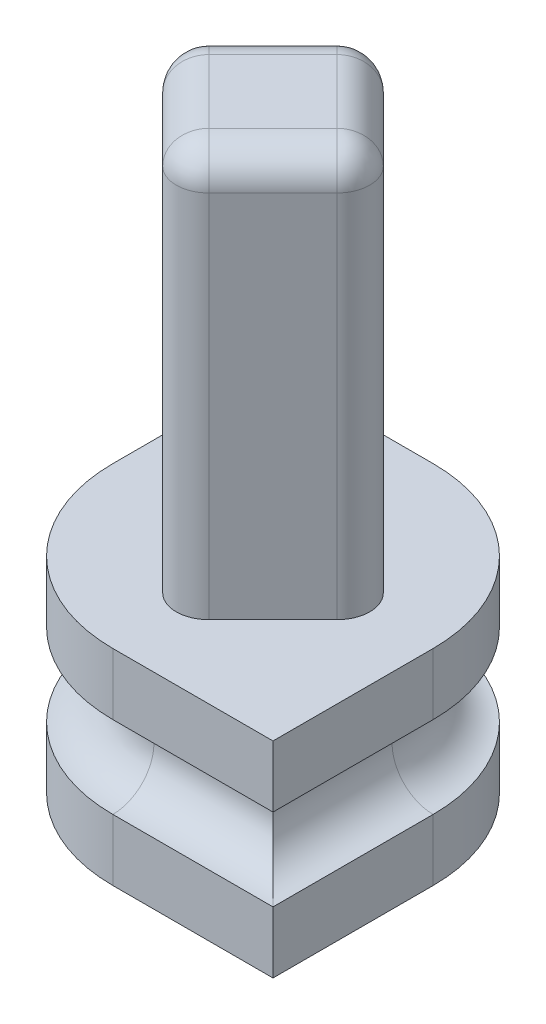
SolidWorks part; units mm, degrees
ref_plane "Front Plane" through (0, 0, 0) normal (0, 0, 1) x (1, 0, 0)
ref_plane "Top Plane" through (0, 0, 0) normal (0, 1, 0) x (1, 0, 0)
ref_plane "Right Plane" through (0, 0, 0) normal (1, 0, 0) x (0, 0, -1)
sketch "Sketch1" plane through (0, 0, 0) normal (0, 1, 0) x (1, 0, 0)
  line L1 (-3.9, 3.9) -> (0, 3.9)
  line L2 (-3.9, 3.9) -> (-3.9, 0)
  line L3 (0, -3.9) -> (3.9, -3.9)
  line L4 (3.9, 0) -> (3.9, -3.9)
  arc A0 (-3.9, 0) -> (0, -3.9) centre (0, 0) ccw
  arc A1 (3.9, 0) -> (0, 3.9) centre (0, 0) ccw
  point P0 (0, 0)
  dimension "D3" = 3.9
  dimension "D4" = 3.9
  dimension "D1" = 7.8
  dimension "D2" = 7.8
  dimension "D5" = 3.9
  dimension "D6" = 3.9
  dimension "D7" = 3.9
  dimension "D8" = 3.9
extrude "Boss-Extrude1" add sketch "Sketch1" along normal blind 5
sketch "Sketch2" plane through (0, 5, 0) normal (0, 1, 0) x (1, 0, 0)
  line L0 (-0.5657, 2.1213) -> (-2.1213, 0.5657)
  line L5 (0.5657, 2.1213) -> (2.1213, 0.5657)
  line L6 (-2.1213, -0.5657) -> (-0.5657, -2.1213)
  line L7 (2.1213, -0.5657) -> (0.5657, -2.1213)
  line L8 (0, 2.687) -> (0, -2.687) construction
  line L9 (-2.687, 0) -> (2.687, 0) construction
  arc A1 (-0.5657, -2.1213) -> (0.5657, -2.1213) centre (0, -1.5556) ccw
  arc A2 (2.1213, 0.5657) -> (2.1213, -0.5657) centre (1.5556, 0) cw
  arc A3 (0.5657, 2.1213) -> (-0.5657, 2.1213) centre (0, 1.5556) ccw
  arc A4 (-2.1213, 0.5657) -> (-2.1213, -0.5657) centre (-1.5556, 0) ccw
  point P1 (0, 0)
  dimension "D1" = 3.8
  dimension "D3" = 0.8
  dimension "D2" = 3.8
extrude "Boss-Extrude2" add sketch "Sketch2" along normal blind 9.8
ref_plane "Plane1" through (0, 2.5, 0) normal (0, 1, 0) x (1, 0, 0)
sketch "Sketch3" plane through (0, 2.5, 0) normal (0, 1, 0) x (1, 0, 0)
  line L0 (-3.9, 0) -> (-3.9, 3.9)
  line L1 (-3.9, 3.9) -> (0, 3.9)
  line L2 (3.9, 0) -> (3.9, -3.9)
  line L3 (3.9, -3.9) -> (0, -3.9)
  line L4 (-2.9, 0) -> (-2.9, 2.9)
  line L5 (-2.9, 2.9) -> (0, 2.9)
  line L6 (2.9, 0) -> (2.9, -2.9)
  line L7 (2.9, -2.9) -> (0, -2.9)
  arc A0 (-3.9, 0) -> (0, -3.9) centre (0, 0) ccw
  arc A1 (3.9, 0) -> (0, 3.9) centre (0, 0) ccw
  arc A2 (2.9, 0) -> (0, 2.9) centre (0, 0) ccw
  arc A3 (-2.9, 0) -> (0, -2.9) centre (0, 0) ccw
  dimension "D1" = 1
extrude "Cut-Extrude2" cut sketch "Sketch3" against normal blind 1 and the other way blind 1
fillet "Fillet1" radius 1 12 edges at (2.9, 3.5, 1.45) (2.0506, 3.5, -2.0506) (1.45, 3.5, 2.9) (-2.0506, 3.5, 2.0506) (2.9, 1.5, 1.45) (2.0506, 1.5, -2.0506) (-2.9, 1.5, -1.45) (1.45, 1.5, 2.9) (-1.45, 3.5, -2.9) (-2.9, 3.5, -1.45) (-1.45, 1.5, -2.9) (-2.0506, 1.5, 2.0506)
fillet "Fillet3" radius 0.8 8 edges at (-1.3435, 14.8, 1.3435) (-2.3556, 14.8, 0) (-1.3435, 14.8, -1.3435) (0, 14.8, -2.3556) (1.3435, 14.8, -1.3435) (2.3556, 14.8, 0) (1.3435, 14.8, 1.3435) (0, 14.8, 2.3556)
